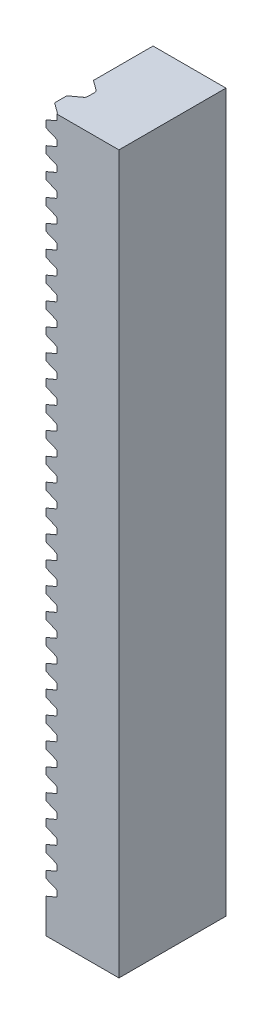
SolidWorks part; units mm, degrees
ref_plane "Front Plane" through (0, 0, 0) normal (0, 0, 1) x (1, 0, 0)
ref_plane "Top Plane" through (0, 0, 0) normal (0, 1, 0) x (1, 0, 0)
ref_plane "Right Plane" through (0, 0, 0) normal (1, 0, 0) x (0, 0, -1)
ref_axis "Axis1" through (0, -55, 0) along (0, 1, 0)
sketch "SketchCI.m_strSketchName" plane through (0, 0, 0) normal (0, 0, 1) x (1, 0, 0)
  line L0 (-1.3856, 3.1416) -> (-1.3856, -197.9203)
  line L1 (-1.3856, -197.9203) -> (19.05, -197.9203)
  line L2 (19.05, -197.9203) -> (19.05, 3.1416)
  line L3 (19.05, 3.1416) -> (-1.3856, 3.1416)
  dimension "D1" = 1.3856
  dimension "D2" = 197.9203
  dimension "D3" = 19.05
  dimension "D4" = 3.1416
extrude "ExtrudeCI" add sketch "SketchCI.m_strSketchName" along normal blind 15 and the other way blind 15
ref_axis "Axis2" through (20.0718, 0, 0) along (-1, 0, 0)
ref_plane "Plane1" through (0, 0, 0) normal (0, 0.5, 0.866) x (1, 0, 0)
sketch "RackToothSketch" plane through (0, 0, 0) normal (0, 0.5, 0.866) x (1, 0, 0)
  line L0 (-1.3856, 1.8647) -> (-1.3856, -1.8647)
  line L1 (-1.3856, -1.8647) -> (1.3902, -0.8544)
  line L2 (1.7321, -0.3661) -> (1.7321, 0.3661)
  line L3 (1.3902, 0.8544) -> (-1.3856, 1.8647)
  arc A0 (1.3902, -0.8544) -> (1.7321, -0.3661) centre (1.2124, -0.3661) ccw
  arc A1 (1.7321, 0.3661) -> (1.3902, 0.8544) centre (1.2124, 0.3661) ccw
  dimension "D1" = 1.0392
  dimension "D2" = 1.0392
  dimension "ADDENDUM" = 1.3856
  dimension "FLANKONE" = 1.2783
  dimension "FLANKONEANGLE" = 70
  dimension "DEDENDUM" = 1.7321
  dimension "FLANKTWO" = 1.2783
  dimension "FLANKTWOANGLE" = 70
extrude "HelicalToothCut" cut sketch "RackToothSketch" against normal blind 30 and the other way blind 30
pattern_linear "PatternSpurGear" count 32 spacing 6.2832 along (0, -1, 0) of "HelicalToothCut"
sketch "AuxiliarySketchSpurGear" plane through (0, 0, 0) normal (0, 0, 1) x (1, 0, 0)
  line L0 (0, 0) -> (0, -201.0619) construction
